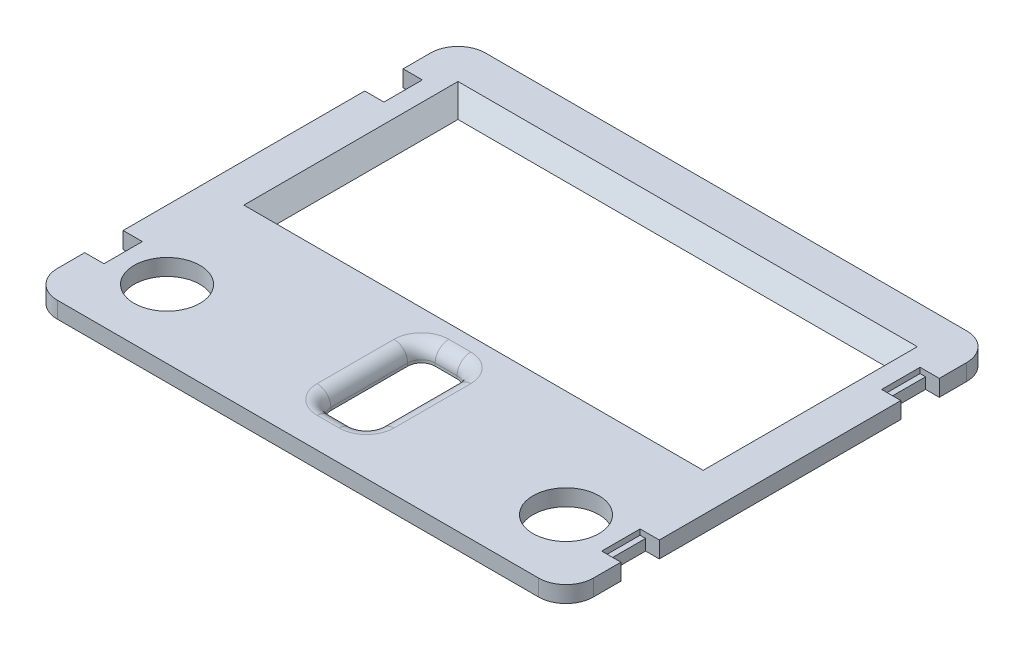
SolidWorks part; units mm, degrees
ref_plane "Front Plane" through (0, 0, 0) normal (0, 0, 1) x (1, 0, 0)
ref_plane "Top Plane" through (0, 0, 0) normal (0, 1, 0) x (1, 0, 0)
ref_plane "Right Plane" through (0, 0, 0) normal (1, 0, 0) x (0, 0, -1)
sketch "Ecran" plane through (0, 0, 0) normal (0, 1, 0) x (1, 0, 0)
  line L0 (0, -55) -> (0, 55) construction
  line L1 (-38.85, 0) -> (38.85, 0)
  line L2 (-38.85, 0) -> (-38.85, -33.02)
  line L3 (-38.85, -33.02) -> (38.85, -33.02)
  line L4 (38.85, 0) -> (38.85, -33.02)
  line L6 (-38.85, -16.51) -> (38.85, -16.51) construction
  line L7 (-48.85, 10) -> (48.85, 10)
  line L8 (-48.85, 10) -> (-48.85, -68.02)
  line L9 (-48.85, -68.02) -> (48.85, -68.02)
  line L10 (48.85, 10) -> (48.85, -68.02)
  line L11 (-4.5, -41.02) -> (4.5, -41.02)
  line L12 (-4.5, -41.02) -> (-4.5, -60.02)
  line L13 (-4.5, -60.02) -> (4.5, -60.02)
  line L14 (4.5, -41.02) -> (4.5, -60.02)
  circle A6 centre (-36.35, -55.52) radius 6
  circle A7 centre (36.35, -55.52) radius 6
  point P6 (0, 0)
  point P30 (0, -41.02)
  dimension "D13" = 19
  dimension "D16" = 12
  dimension "D1" = 33.02
  dimension "D2" = 77.7
  dimension "D6" = 10
  dimension "D7" = 10
  dimension "D8" = 10
  dimension "D10" = 12.5
  dimension "D11" = 12.5
  dimension "D12" = 35
  dimension "D14" = 8
  dimension "D15" = 9
extrude "Boss-Extrude1" add sketch "Ecran" along normal blind 3
chamfer "Chamfer1" distance 3 angle 45 4 edges at (0, 3, 33.02) (38.85, 3, 16.51) (-38.85, 3, 16.51) (0, 3, 0)
fillet "Fillet1" radius 5 4 edges at (48.85, 1.5, 68.02) (-48.85, 1.5, 68.02) (-48.85, 1.5, -10) (48.85, 1.5, -10)
sketch "Sketch2" plane through (0, 3, 0) normal (0, 1, 0) x (1, 0, 0)
  line L0 (48.85, -51.02) -> (46.35, -51.02)
  line L1 (-48.85, 5) -> (-48.85, -63.02) construction
  line L2 (-48.85, 0) -> (-46.35, 0)
  line L3 (-48.85, 0) -> (-48.85, -7)
  line L4 (-48.85, -7) -> (-46.35, -7)
  line L5 (-46.35, 0) -> (-46.35, -7)
  line L6 (43.85, 10) -> (-43.85, 10) construction
  line L7 (0, -55) -> (0, 55) construction
  line L8 (46.35, 0) -> (46.35, -7)
  line L9 (48.85, 0) -> (46.35, 0)
  line L10 (48.85, 0) -> (48.85, -7)
  line L11 (48.85, -7) -> (46.35, -7)
  line L12 (-76.4295, -29.01) -> (85.0476, -29.01) construction
  line L13 (48.85, -58.02) -> (48.85, -51.02)
  line L14 (48.85, -58.02) -> (46.35, -58.02)
  line L15 (46.35, -58.02) -> (46.35, -51.02)
  line L16 (-46.35, -58.02) -> (-46.35, -51.02)
  line L17 (-48.85, -58.02) -> (-48.85, -51.02)
  line L18 (-48.85, -58.02) -> (-46.35, -58.02)
  line L19 (-48.85, -51.02) -> (-46.35, -51.02)
  dimension "D1" = 10
  dimension "D2" = 7
  dimension "D3" = 2.5
  dimension "D4" = 39.01
extrude "Cut-Extrude1" cut sketch "Sketch2" against normal through all
sketch "Sketch3" plane through (0, 3, 0) normal (0, 1, 0) x (1, 0, 0)
  line L1 (-46.35, 0) -> (-45.35, 0)
  line L2 (-46.35, 0) -> (-46.35, -7)
  line L3 (-46.35, -7) -> (-45.35, -7)
  line L4 (-45.35, 0) -> (-45.35, -7)
  line L5 (43.85, 10) -> (-43.85, 10) construction
  line L6 (-48.85, 5) -> (-48.85, 0) construction
  line L7 (-79.2244, -29.01) -> (90.4537, -29.01) construction
  line L8 (-45.35, -58.02) -> (-45.35, -51.02)
  line L9 (-46.35, -51.02) -> (-45.35, -51.02)
  line L10 (-46.35, -58.02) -> (-46.35, -51.02)
  line L11 (-46.35, -58.02) -> (-45.35, -58.02)
  line L12 (0, -55) -> (0, 55) construction
  line L13 (46.35, -58.02) -> (45.35, -58.02)
  line L14 (46.35, -58.02) -> (46.35, -51.02)
  line L15 (46.35, -51.02) -> (45.35, -51.02)
  line L16 (45.35, -58.02) -> (45.35, -51.02)
  line L17 (45.35, 0) -> (45.35, -7)
  line L18 (46.35, -7) -> (45.35, -7)
  line L19 (46.35, 0) -> (46.35, -7)
  line L20 (46.35, 0) -> (45.35, 0)
  dimension "D1" = 7
  dimension "D2" = 10
  dimension "D3" = 2.5
  dimension "D4" = 1
  dimension "D5" = 39.01
extrude "Cut-Extrude2" cut sketch "Sketch3" against normal blind 1
fillet "Fillet2" radius 2.5 4 edges at (4.5, 1.5, 60.02) (-4.5, 1.5, 60.02) (4.5, 1.5, 41.02) (-4.5, 1.5, 41.02)
fillet "Fillet3" radius 2.5 8 edges at (-3.7678, 3, 41.7522) (0, 3, 41.02) (3.7678, 3, 41.7522) (4.5, 3, 50.52) (3.7678, 3, 59.2878) (0, 3, 60.02) (-3.7678, 3, 59.2878) (-4.5, 3, 50.52)
equation "\"1po\"=1"
